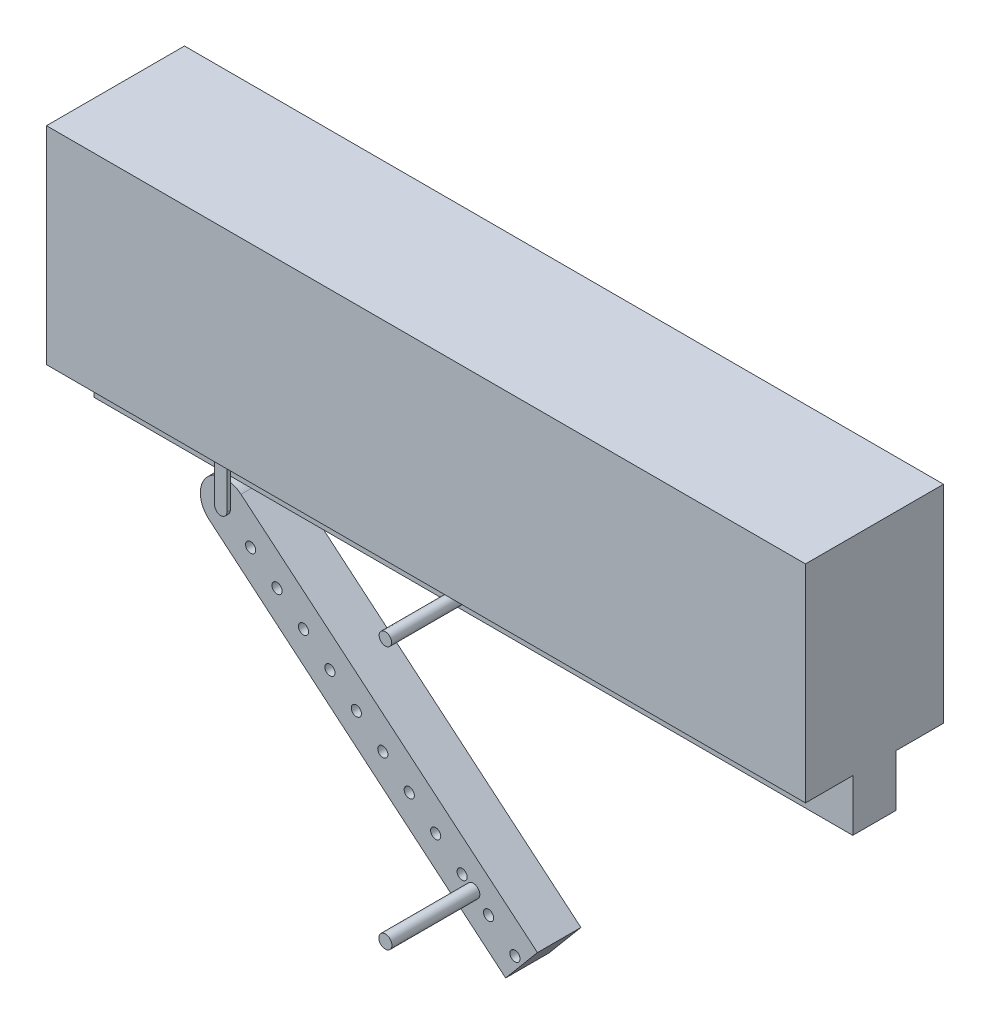
SolidWorks part; units mm, degrees
ref_plane "Plan de face" through (0, 0, 0) normal (0, 0, 1) x (1, 0, 0)
ref_plane "Plan de dessus" through (0, 0, 0) normal (0, 1, 0) x (1, 0, 0)
ref_plane "Plan de droite" through (0, 0, 0) normal (1, 0, 0) x (0, 0, -1)
ref_plane "Plan5" through (237.5, 0, 0) normal (-1, 0, 0) x (0, 0, 1)
sketch "Esquisse7" plane through (237.5, 0, 0) normal (-1, 0, 0) x (0, 0, 1)
  line L0 (135.5851, 602.1492) -> (198.5851, 602.1492)
  line L1 (135.5851, 602.1492) -> (135.5851, 677.1492)
  line L2 (198.5851, 602.1492) -> (198.5851, 677.1492)
  line L3 (135.5851, 677.1492) -> (198.5851, 677.1492)
  line L5 (135.5851, 677.1492) -> (198.5851, 602.1492) construction
  line L6 (198.5851, 677.1492) -> (135.5851, 602.1492) construction
  dimension "D1" = 63
  dimension "D2" = 75
sketch "Esquisse8" plane through (475, 0, 0) normal (-1, 0, 0) x (0, 0, 1)
  line L0 (263, 600) -> (63, 675) construction
  line L1 (63, 600) -> (263, 675) construction
extrude "Boss.-Extru.4" add sketch "Esquisse7" along normal blind 550 and the other way blind 550 separate body
sketch "Esquisse3" plane through (0, 0, 326) normal (0, 0, 1) x (1, 0, 0)
  line L0 (75, 675) -> (75, 600) construction
  line L1 (75, 675) -> (475, 675) construction
  line L2 (75, 637.5) -> (476.0322, 637.5) construction
  line L3 (200, 600) -> (275, 675) construction
  circle A0 centre (237.5, 637.5) radius 10
extrude "Enlèv. mat.-Extru.2" cut sketch "Esquisse3" against normal through all
sketch "Esquisse11" plane through (0, 0, 198.5851) normal (0, 0, 1) x (1, 0, 0)
  line L1 (-99.1531, 586.9143) -> (330.5036, 226.557)
  line L2 (-145.2214, 531.9867) -> (284.4353, 171.6294)
  line L3 (330.5036, 226.557) -> (284.4353, 171.6294)
  line L4 (-122.1872, 559.4505) -> (-122.1872, 643.6137) construction
  line L5 (-114.55, 559.4505) -> (-114.55, 643.6137)
  line L7 (-132.34, 643.6137) -> (-132.34, 559.4505)
  arc A0 (-99.1531, 586.9143) -> (-145.2214, 531.9867) centre (-122.1872, 559.4505) ccw
  arc A1 (-132.34, 559.4505) -> (-114.55, 559.4505) centre (-123.445, 559.4505) ccw
  arc A2 (-114.55, 643.6137) -> (-132.34, 643.6137) centre (-123.445, 643.6137) ccw
  line M4 (-312.5, 602.1492) -> (787.5, 602.1492)
extrude "Boss.-Extru.5" add sketch "Esquisse11" against normal blind 63 separate body contours A1 L7 A0 L2 L3 L1 L5 | L7 A1 L5 A0 region at (85.5513, 384.9787, 198.5851) region at (-123.4228, 573.6379, 198.5851)
extrude "Boss.-Extru.6" add sketch "Esquisse11<3>" along normal blind 5 contours L5 A2 L7 M4 | L7 A1 L5 A0 | A0 L4 L7 M4 | L4 A0 L5 M4 region at (-118.2953, 598.5813, 198.5851) region at (-123.4228, 573.6379, 198.5851) region at (-123.445, 626.4152, 198.5851) region at (-127.4321, 598.4665, 198.5851)
sketch "Esquisse11<3>" plane through (0, 0, 198.5851) normal (0, 0, 1) x (1, 0, 0) same geometry as "Esquisse11"
sketch "Esquisse12" plane through (0, 0, 198.5851) normal (0, 0, 1) x (1, 0, 0)
  line L2 (307.4695, 199.0932) -> (-123.445, 559.4505) construction
  line L3 (330.5036, 226.557) -> (284.4353, 171.6294) construction
  circle A0 centre (-123.445, 559.4505) radius 7.3554
extrude "Enlèv. mat.-Extru.3" cut sketch "Esquisse12" against normal blind 100
pattern_linear "Répétition linéaire2" count 12 spacing 50 along (0.7662, -0.6426, 0) of "Enlèv. mat.-Extru.3"
sketch "Esquisse13" plane through (0, 0, 326) normal (0, 0, 1) x (1, 0, 0)
  line L0 (237.5, 144.65) -> (237.5, -144.65) construction
  circle A0 centre (237.5, 257.6084) radius 9.504
extrude "Boss.-Extru.7" add sketch "Esquisse13" against normal through all
pattern_linear "Répétition linéaire3" count 2 spacing 66 along (0, 0, -1) of "Boss.-Extru.6"
sketch "Esquisse14" plane through (0, 0, 326) normal (0, 0, 1) x (1, 0, 0)
  circle A0 centre (237.5, 637.5) radius 9
extrude "Boss.-Extru.8" add sketch "Esquisse14" against normal blind 326 separate body
sketch "Esquisse15" plane through (-312.5, 0, 0) normal (-1, 0, 0) x (0, 0, 1)
  line L0 (198.5851, 677.1492) -> (135.5851, 677.1492) construction
  line L1 (67.0851, 677.1492) -> (267.0851, 677.1492)
  line L2 (67.0851, 677.1492) -> (67.0851, 977.1492)
  line L3 (67.0851, 977.1492) -> (267.0851, 977.1492)
  line L4 (267.0851, 677.1492) -> (267.0851, 977.1492)
  point P7 (167.0851, 677.1492)
  dimension "D1" = 300
  dimension "D2" = 200
extrude "Boss.-Extru.9" add sketch "Esquisse15" against normal blind 1100
